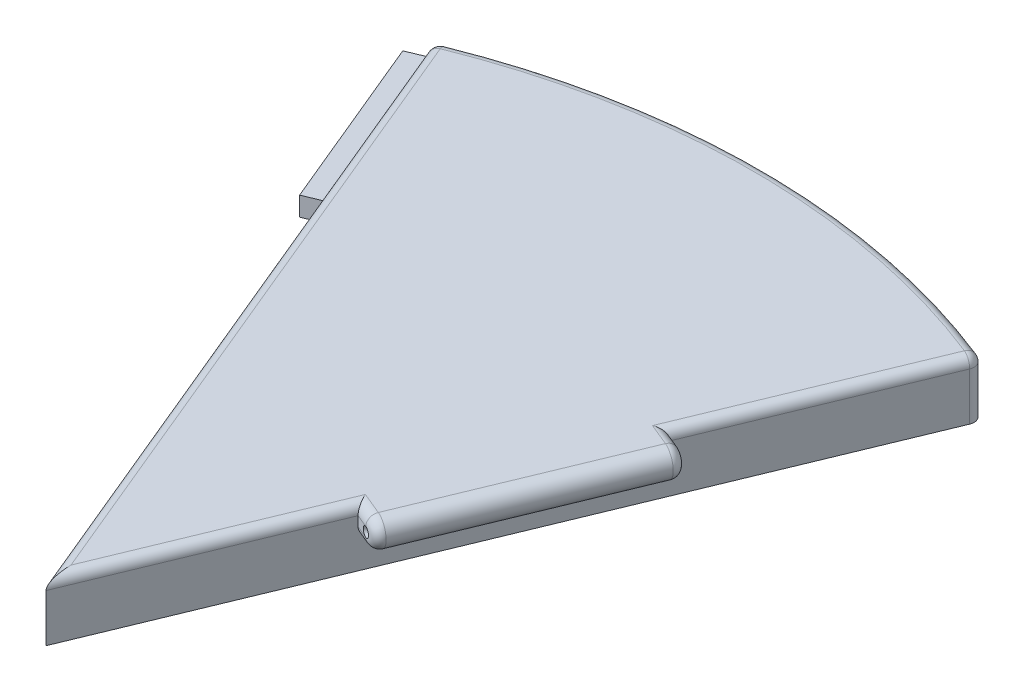
SolidWorks part; units mm, degrees
ref_plane "Front Plane" through (0, 0, 0) normal (0, 0, 1) x (1, 0, 0)
ref_plane "Top Plane" through (0, 0, 0) normal (0, 1, 0) x (1, 0, 0)
ref_plane "Right Plane" through (0, 0, 0) normal (1, 0, 0) x (0, 0, -1)
sketch "Sketch2" plane through (0, 0, 0) normal (0, 1, 0) x (1, 0, 0)
  line L0 (28.6256, 69.3223) -> (0, 0)
  line L1 (28.6256, 69.3223) -> (-28.7769, 69.2596)
  line L2 (-28.7769, 69.2596) -> (-69.3223, 28.6256)
  line L3 (-69.3223, 28.6256) -> (-69.2596, -28.7769)
  line L4 (-69.2596, -28.7769) -> (-28.6256, -69.3223)
  line L5 (-28.6256, -69.3223) -> (28.7769, -69.2596)
  line L6 (28.7769, -69.2596) -> (69.3223, -28.6256)
  line L7 (69.3223, -28.6256) -> (69.2596, 28.7769)
  line L8 (69.2596, 28.7769) -> (28.6256, 69.3223)
  line L9 (0, 0) -> (-28.7769, 69.2596)
  circle A0 centre (0, 0) radius 75 construction
  arc A1 (-28.7769, 69.2596) -> (28.6256, 69.3223) centre (0, 0) cw
  dimension "D1" = 75
extrude "Boss-Extrude1" add sketch "Sketch2" along normal blind 6 contours A1 L1 | L9 L0 L1 region at (-0.0504, 0, -46.1939) region at (-0.0781, 0, -71.5822)
sketch "Sketch3" plane through (0, 0, 0) normal (0.9243, 0, 0.3817) x (0.3817, 0, -0.9243)
  line L0 (75, 6) -> (0, 6) construction
  line L1 (25, 6) -> (50, 6)
  line L2 (25, 6) -> (25, 3)
  line L3 (25, 3) -> (50, 3)
  line L4 (50, 6) -> (50, 3)
  dimension "D1" = 3
  dimension "D2" = 25
  dimension "D3" = 25
extrude "Boss-Extrude2" add sketch "Sketch3" along normal blind 3
sketch "Sketch4" plane through (9.5419, 0, -23.1074) normal (-0.3817, 0, 0.9243) x (0.9243, 0, 0.3817)
  line L0 (3, 6) -> (3, 3) construction
  line L1 (3, 6) -> (0, 6) construction
  circle A0 centre (1.5, 4.5) radius 1.5 construction
  circle A1 centre (1.5, 4.5) radius 0.5
  dimension "D1" = 1.5
  dimension "D2" = 1.5
extrude "Cut-Extrude2" cut sketch "Sketch4" against normal blind 25
sketch "Sketch8" plane through (9.5419, 0, -23.1074) normal (-0.3817, 0, 0.9243) x (0.9243, 0, 0.3817)
  line L0 (1.5, 6) -> (3.4605, 6)
  line L1 (3, 6) -> (0, 6) construction
  line L2 (3.4605, 6) -> (3.4605, 3)
  line L3 (3.4605, 3) -> (1.5, 3)
  line L4 (3, 3) -> (0, 3) construction
  arc A0 (1.5, 3) -> (1.5, 6) centre (1.5, 4.5) ccw
extrude "Cut-Extrude3" cut sketch "Sketch8" against normal blind 25
fillet "Fillet1" radius 1 12 edges at (19.777, 3, -45.9286) (21.8566, 4.5, -45.0698) (10.2351, 3, -22.8212) (12.3148, 4.5, -21.9624) (4.7709, 6, -11.5537) (-14.3884, 6, -34.6298) (-0.0819, 6, -75) (23.8547, 6, -57.7685) (19.777, 6, -45.9286) (10.2351, 6, -22.8212) (28.6256, 3, -69.3223) (-28.7769, 3, -69.2596)
sketch "Sketch9" plane through (0, 0, 0) normal (-0.9235, 0, 0.3837) x (0.3837, 0, 0.9235)
  line L1 (-73.9932, 5) -> (-53.9932, 5)
  line L2 (-73.9932, 5) -> (-73.9932, 3)
  line L3 (-73.9932, 3) -> (-53.9932, 3)
  line L4 (-53.9932, 5) -> (-53.9932, 3)
  dimension "D1" = 2
  dimension "D2" = 20
extrude "Boss-Extrude3" add sketch "Sketch9" along normal blind 2
